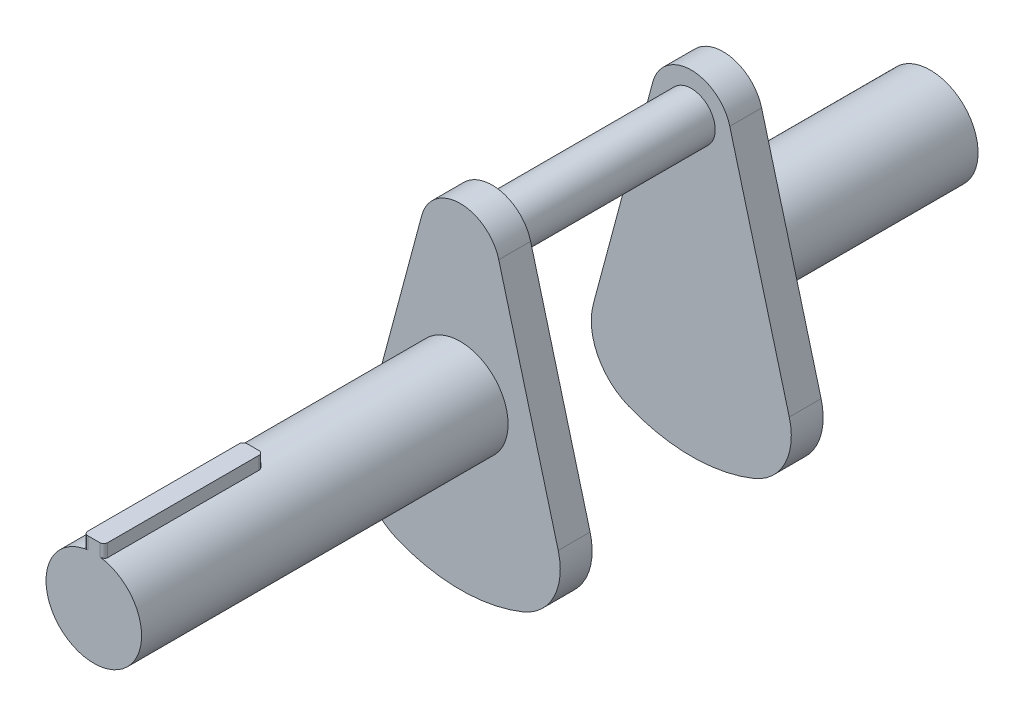
SolidWorks part; units mm, degrees
material "Alloy Steel"
ref_plane "Front Plane" through (0, 0, 0) normal (0, 0, 1) x (1, 0, 0)
ref_plane "Top Plane" through (0, 0, 0) normal (0, 1, 0) x (1, 0, 0)
ref_plane "Right Plane" through (0, 0, 0) normal (1, 0, 0) x (0, 0, -1)
sketch "Sketch1" plane through (0, 0, 0) normal (0, 0, 1) x (1, 0, 0)
  circle A0 centre (0, 0) radius 6
  dimension "D1" = 12
extrude "Boss-Extrude1" add sketch "Sketch1" along normal mid plane 50
sketch "Sketch2" plane through (0, 0, 25) normal (0, 0, 1) x (1, 0, 0)
  line L0 (9.6593, 2.5882) -> (24.5955, -53.1548)
  line L1 (0, 0) -> (0, -15.7002) construction
  line L2 (-9.6593, 2.5882) -> (-24.5955, -53.1548)
  line L4 (-2.5, -20.2633) -> (-2.5, -17)
  line L5 (-2.5, -17) -> (2.5, -17)
  line L6 (2.5, -20.2633) -> (2.5, -17)
  arc A0 (-15.7215, -70.9466) -> (15.7215, -70.9466) centre (0, -32) ccw
  arc A1 (-2.5, -20.2633) -> (2.5, -20.2633) centre (0, -32) ccw
  arc A2 (9.6593, 2.5882) -> (-9.6593, 2.5882) centre (0, 0) ccw
  arc A3 (15.7215, -70.9466) -> (24.5955, -53.1548) centre (10.1067, -57.0371) ccw
  arc A4 (-15.7215, -70.9466) -> (-24.5955, -53.1548) centre (-10.1067, -57.0371) cw
  arc A5 (2.5, -20.2633) -> (-2.5, -20.2633) centre (0, -32) ccw
  point P5 (0, -32)
  point P12 (0, -20)
  circle M2 centre (0, 0) radius 6
  dimension "D2" = 12
  dimension "D3" = 20
  dimension "D5" = 30
  dimension "D6" = 42
  dimension "D7" = 15
  dimension "D1" = 32
  dimension "D4" = 15
  dimension "D8" = 15
  dimension "D9" = 5
extrude "Boss-Extrude3" add sketch "Sketch2" along normal blind 8 contours M2 | L4 A1 L6 L5 | A4 A0 A3 L0 A2 L2 A1 L4 L5 L6 M2 region at (16.1821, -25.5366, 25) region at (0, -18.5447, 25) region at (0, 0, 25)
extrude "Boss-Extrude4" add sketch "Sketch2<5>" along normal blind 100 contours A1 A5 region at (0, -32, 25)
sketch "Sketch2<5>" plane through (0, 0, 25) normal (0, 0, 1) x (1, 0, 0) same geometry as "Sketch2"
sketch "Sketch3" plane through (0, 0, 125) normal (0, 0, 1) x (1, 0, 0)
  line L0 (2.5, -20.2633) -> (2.5, -17) construction
  line L1 (-2.5, -17) -> (2.5, -17) construction
  line L2 (-2.5, -20.2633) -> (-2.5, -17) construction
  line L3 (-9.6593, 2.5882) -> (-24.5955, -53.1548) construction
  line L4 (9.6593, 2.5882) -> (24.5955, -53.1548) construction
  line L5 (2.5, -20.2633) -> (2.5, -17)
  line L6 (-2.5, -17) -> (2.5, -17)
  line L7 (-2.5, -20.2633) -> (-2.5, -17)
  line L8 (-9.6593, 2.5882) -> (-24.5955, -53.1548)
  line L9 (9.6593, 2.5882) -> (24.5955, -53.1548)
  arc A0 (2.5, -20.2633) -> (-2.5, -20.2633) centre (0, -32) ccw construction
  arc A1 (-2.5, -20.2633) -> (2.5, -20.2633) centre (0, -32) ccw construction
  arc A2 (-24.5955, -53.1548) -> (-15.7215, -70.9466) centre (-10.1067, -57.0371) ccw construction
  arc A3 (-15.7215, -70.9466) -> (15.7215, -70.9466) centre (0, -32) ccw construction
  arc A4 (15.7215, -70.9466) -> (24.5955, -53.1548) centre (10.1067, -57.0371) ccw construction
  arc A5 (9.6593, 2.5882) -> (-9.6593, 2.5882) centre (0, 0) ccw construction
  arc A6 (2.5, -20.2633) -> (-2.5, -20.2633) centre (0, -32) ccw
  arc A7 (-2.5, -20.2633) -> (2.5, -20.2633) centre (0, -32) ccw
  arc A8 (-24.5955, -53.1548) -> (-15.7215, -70.9466) centre (-10.1067, -57.0371) ccw
  arc A9 (-15.7215, -70.9466) -> (15.7215, -70.9466) centre (0, -32) ccw
  arc A10 (15.7215, -70.9466) -> (24.5955, -53.1548) centre (10.1067, -57.0371) ccw
  arc A11 (9.6593, 2.5882) -> (-9.6593, 2.5882) centre (0, 0) ccw
  circle M1 centre (0, -32) radius 12
extrude "Boss-Extrude5" add sketch "Sketch3" against normal blind 40 contours L7 L5 L6 M1 region at (0, -18.5447, 125)
sketch "Sketch4" plane through (0, 0, -25) normal (0, 0, -1) x (-1, 0, 0)
  line L0 (-2.5, -20.2633) -> (-2.5, -17) construction
  line L1 (2.5, -17) -> (-2.5, -17) construction
  line L2 (2.5, -20.2633) -> (2.5, -17) construction
  line L3 (9.6593, 2.5882) -> (24.5955, -53.1548) construction
  line L4 (-9.6593, 2.5882) -> (-24.5955, -53.1548) construction
  line L5 (-2.5, -20.2633) -> (-2.5, -17)
  line L6 (2.5, -17) -> (-2.5, -17)
  line L7 (2.5, -20.2633) -> (2.5, -17)
  line L8 (9.6593, 2.5882) -> (24.5955, -53.1548)
  line L9 (-9.6593, 2.5882) -> (-24.5955, -53.1548)
  arc A0 (2.5, -20.2633) -> (-2.5, -20.2633) centre (0, -32) ccw construction
  arc A1 (-2.5, -20.2633) -> (2.5, -20.2633) centre (0, -32) ccw construction
  arc A2 (15.7215, -70.9466) -> (24.5955, -53.1548) centre (10.1067, -57.0371) ccw construction
  arc A3 (-15.7215, -70.9466) -> (15.7215, -70.9466) centre (0, -32) ccw construction
  arc A4 (-24.5955, -53.1548) -> (-15.7215, -70.9466) centre (-10.1067, -57.0371) ccw construction
  arc A5 (9.6593, 2.5882) -> (-9.6593, 2.5882) centre (0, 0) ccw construction
  arc A6 (2.5, -20.2633) -> (-2.5, -20.2633) centre (0, -32) ccw
  arc A7 (-2.5, -20.2633) -> (2.5, -20.2633) centre (0, -32) ccw
  arc A8 (15.7215, -70.9466) -> (24.5955, -53.1548) centre (10.1067, -57.0371) ccw
  arc A9 (-15.7215, -70.9466) -> (15.7215, -70.9466) centre (0, -32) ccw
  arc A10 (-24.5955, -53.1548) -> (-15.7215, -70.9466) centre (-10.1067, -57.0371) ccw
  arc A11 (9.6593, 2.5882) -> (-9.6593, 2.5882) centre (0, 0) ccw
  circle M1 centre (0, 0) radius 6
extrude "Boss-Extrude7" add sketch "Sketch4" along normal blind 8 contours A6 A7 | L8 A11 L9 A10 A9 A8 A7 L5 L6 L7 M1 | A6 L7 L6 L5 | M1 region at (0, -18.5447, -25) region at (0, -32, -25) region at (-16.1821, -25.5366, -25) region at (0, 0, -25)
extrude "Boss-Extrude8" add sketch "Sketch4<4>" along normal blind 60 contours A6 A7 region at (0, -32, -25)
sketch "Sketch4<4>" plane through (0, 0, -25) normal (0, 0, -1) x (-1, 0, 0) same geometry as "Sketch4"
fillet "Fillet1" radius 1 4 edges at (2.5, -18.6317, 85) (-2.5, -18.6317, 85) (2.5, -18.6317, 125) (-2.5, -18.6317, 125)
